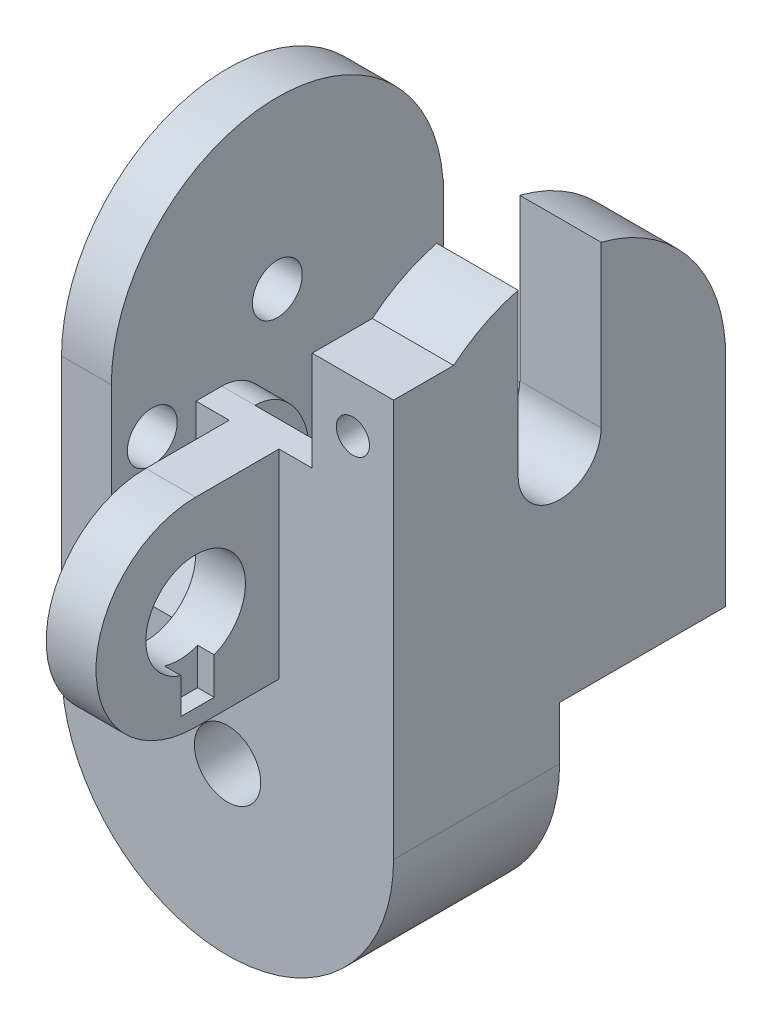
SolidWorks part; units mm, degrees
ref_plane "Front Plane" through (0, 0, 0) normal (0, 0, 1) x (1, 0, 0)
ref_plane "Top Plane" through (0, 0, 0) normal (0, 1, 0) x (1, 0, 0)
ref_plane "Right Plane" through (0, 0, 0) normal (1, 0, 0) x (0, 0, -1)
sketch "Sketch1" plane through (0, 0, 0) normal (1, 0, 0) x (0, 0, -1)
  arc A0 (9.7654, 20.1165) -> (-9.7654, 20.1165) centre (0, 22.2701) ccw
  arc A1 (-7.8874, -56.3924) -> (7.8874, -56.3924) centre (0, -57.7299) ccw
  arc A2 (-7.8874, -56.3924) -> (-9.7654, 20.1165) centre (-205.0724, -22.9549) ccw
  circle A3 centre (0, 22.2701) radius 1.5
  arc A4 (9.7654, 20.1165) -> (7.8874, -56.3924) centre (205.0724, -22.9549) ccw
  circle A5 centre (0, -57.7299) radius 2.5
extrude "Boss-Extrude1" add sketch "Sketch1" along normal blind 20
sketch "Sketch2" plane through (0, 0, 0) normal (0, 0, 1) x (1, 0, 0)
  line L1 (0, -65.7299) -> (8.1, -65.7299)
  line L2 (0, -65.7299) -> (0, -45.7299)
  line L3 (0, -45.7299) -> (8.1, -45.7299)
  line L4 (8.1, -65.7299) -> (8.1, -45.7299)
  line L5 (20, -65.7299) -> (14.8, -65.7299)
  line L6 (20, -65.7299) -> (20, -45.7299)
  line L7 (20, -45.7299) -> (14.8, -45.7299)
  line L8 (14.8, -65.7299) -> (14.8, -45.7299)
  line L11 (3, 32.2701) -> (8.1, 32.2701)
  line L12 (3, 32.2701) -> (3, 12.2701)
  line L13 (3, 12.2701) -> (8.1, 12.2701)
  line L14 (8.1, 32.2701) -> (8.1, 12.2701)
extrude "Cut-Extrude1" cut sketch "Sketch2" against normal blind 20 and the other way blind 20
sketch "Sketch3" plane through (8.1, 0, 0) normal (-1, 0, 0) x (0, 0, 1)
  line L0 (8.5, 22.2701) -> (8.5, 40.9095)
  line L1 (8.5, 40.9095) -> (-17.5287, 40.9095)
  line L2 (-17.5287, 40.9095) -> (-17.5287, 13.7701)
  line L3 (0, 13.7701) -> (-17.5287, 13.7701)
  arc A0 (0, 13.7701) -> (8.5, 22.2701) centre (0, 22.2701) ccw
extrude "Cut-Extrude2" cut sketch "Sketch3" against normal blind 9
sketch "Sketch4" plane through (8.1, 0, 0) normal (-1, 0, 0) x (0, 0, 1)
  line L0 (8.5, 27.5379) -> (8.2838, 12.7416)
  line L1 (8.2838, 12.7416) -> (10.2838, 12.7416)
  line L2 (10.2838, 12.7416) -> (10.2838, 27.5379)
  line L3 (10.2838, 27.5379) -> (8.5, 27.5379)
  arc A0 (9.7654, 20.1165) -> (6.3734, -45.7299) centre (205.0724, -22.9549) ccw construction
extrude "Boss-Extrude2" add sketch "Sketch4" against normal through all
sketch "Sketch5" plane through (8.1, 0, 0) normal (-1, 0, 0) x (0, 0, 1)
  line L4 (8.1452, 11.9686) -> (8.4478, 23.9686)
  line L6 (15.0224, 23.9686) -> (9.8547, 23.9686)
  line L8 (8.1452, 11.9686) -> (15.0224, 11.9686)
  line L9 (8.5, 27.5379) -> (8.4045, 20.9993) construction
  line L10 (8.4478, 23.9686) -> (9.8547, 23.9686)
  circle A2 centre (15.0224, 17.9686) radius 3
  arc A5 (15.0224, 11.9686) -> (15.0224, 23.9686) centre (15.0224, 17.9686) ccw
  arc A6 (9.7654, 20.1165) -> (-9.7654, 20.1165) centre (0, 22.2701) ccw construction
  arc A7 (9.7654, 20.1165) -> (6.3734, -45.7299) centre (205.0724, -22.9549) ccw construction
extrude "Boss-Extrude3" add sketch "Sketch5" against normal blind 5
sketch "Sketch12" plane through (13.1, 0, 0) normal (1, 0, 0) x (0, 0, -1)
  line L2 (-13.9029, 14.9686) -> (-13.9029, 12.9686)
  line L4 (-15.9029, 14.9686) -> (-15.9029, 15.2943)
  line L5 (-15.9029, 15.2943) -> (-13.9029, 15.2943)
  line L6 (-13.9029, 12.9686) -> (-15.9029, 12.9686)
  line L7 (-13.9029, 14.9686) -> (-13.9029, 15.2943)
  line L11 (-15.9029, 14.9686) -> (-15.9029, 12.9686)
extrude "Cut-Extrude6" cut sketch "Sketch12" against normal blind 1
sketch "Sketch13" plane through (17.1, 0, 0) normal (-1, 0, 0) x (0, 0, 1)
  circle A0 centre (0, 22.2701) radius 2.5
extrude "Cut-Extrude7" cut sketch "Sketch13" against normal blind 4
sketch "Sketch15" plane through (0, 0, 0) normal (-1, 0, 0) x (0, 0, 1)
  line L0 (10, 22.2701) -> (10, 11.9686)
  line L1 (8.1452, 11.9686) -> (15.0224, 11.9686) construction
  line L2 (10, 11.9686) -> (8.1452, 11.9686)
  line L3 (10, 22.2701) -> (7.5957, 11.9686)
  line L4 (7.5957, 11.9686) -> (8.1452, 11.9686)
  arc A0 (9.7654, 20.1165) -> (-9.7654, 20.1165) centre (0, 22.2701) ccw construction
extrude "Boss-Extrude4" add sketch "Sketch15" against normal blind 3
sketch "Sketch16" plane through (20, 0, 0) normal (1, 0, 0) x (0, 0, -1)
  line L0 (-10.2838, 23.9686) -> (-9.8547, 23.9686)
  line L1 (-10.2838, 23.9686) -> (-10.2838, 27.5379)
  line L2 (-10.2838, 27.5379) -> (-8.5, 27.5379) construction
  line L3 (-10.2838, 12.7416) -> (-10.2838, 27.5379) construction
  line L4 (-10.2838, 27.5379) -> (-8.5, 27.5379)
  arc A0 (-8.5, 27.5379) -> (-9.8547, 23.9686) centre (0, 22.2701) ccw
extrude "Cut-Extrude9" cut sketch "Sketch16" against normal blind 3
sketch "Sketch17" plane through (0, 0, 10.2838) normal (0, 0, 1) x (1, 0, 0)
  line L1 (17.1, 27.5379) -> (8.1, 27.5379)
  line L2 (17.1, 27.5379) -> (17.1, 23.9686)
  line L3 (17.1, 23.9686) -> (8.1, 23.9686)
  line L4 (8.1, 27.5379) -> (8.1, 23.9686)
extrude "Cut-Extrude11" cut sketch "Sketch17" against normal blind 3
sketch "Sketch18" plane through (13.1, 0, 0) normal (1, 0, 0) x (0, 0, -1)
  line L1 (-10.2838, 12.7416) -> (-4.5128, 12.7416)
  line L2 (-10.2838, 12.7416) -> (-10.2838, 11.9686)
  line L3 (-10.2838, 11.9686) -> (-4.5128, 11.9686)
  line L4 (-4.5128, 12.7416) -> (-4.5128, 11.9686)
extrude "Boss-Extrude5" add sketch "Sketch18" along normal through all and the other way blind 1
sketch "Sketch19" plane through (0, 12.2701, 0) normal (0, 1, 0) x (1, 0, 0)
  line L1 (8.1, -8.1989) -> (3, -8.1989)
  line L2 (8.1, -8.1989) -> (8.1, 8.1989)
  line L3 (8.1, 8.1989) -> (3, 8.1989)
  line L4 (3, -8.1989) -> (3, 8.1989)
extrude "Cut-Extrude12" cut sketch "Sketch19" against normal up to surface (0.3015 mm away) up to face at (1.5, 11.9686, 9.0726)
sketch "Sketch20" plane through (17.1, 0, 0) normal (-1, 0, 0) x (0, 0, 1)
  line L1 (2.5, 22.2701) -> (-2.5, 22.2701)
  line L2 (2.5, 22.2701) -> (2.5, 34.6894)
  line L3 (2.5, 34.6894) -> (-2.5, 34.6894)
  line L4 (-2.5, 22.2701) -> (-2.5, 34.6894)
  circle A0 centre (0, 22.2701) radius 2.5 construction
extrude "Cut-Extrude13" cut sketch "Sketch20" against normal blind 10
sketch "Sketch21" plane through (17.1, 0, 0) normal (-1, 0, 0) x (0, 0, 1)
  line L1 (-8.4732, 13.7701) -> (0.2785, 12.274)
  line L3 (2.5, 22.2701) -> (2.5, 31.9526)
  line L5 (-2.5, 22.2701) -> (-2.5, 31.9526)
  arc A0 (0.2785, 12.274) -> (2.5, 31.9526) centre (0, 22.2701) ccw
  arc A1 (-2.5, 22.2701) -> (2.5, 22.2701) centre (0, 22.2701) ccw
  arc A2 (-2.5, 31.9526) -> (-9.7654, 20.1165) centre (0, 22.2701) ccw
  arc A7 (-8.4732, 13.7701) -> (-9.7654, 20.1165) centre (-205.0724, -22.9549) ccw
extrude "Boss-Extrude6" add sketch "Sketch21" along normal blind 2
sketch "Sketch23" plane through (0, 0, 10.2838) normal (0, 0, 1) x (1, 0, 0)
  line L1 (15.1, 23.9686) -> (20, 23.9686)
  line L2 (15.1, 23.9686) -> (15.1, 29.9686)
  line L3 (15.1, 29.9686) -> (20, 29.9686)
  line L4 (20, 23.9686) -> (20, 29.9686)
extrude "Boss-Extrude7" add sketch "Sketch23" against normal blind 4
sketch "Sketch22" plane through (0, 0, 10.2838) normal (0, 0, 1) x (1, 0, 0)
  circle A1 centre (17.55, 26.8701) radius 1
extrude "Cut-Extrude15" cut sketch "Sketch22" against normal blind 8
sketch "Sketch24" plane through (8.1, 0, 0) normal (-1, 0, 0) x (0, 0, 1)
  line L0 (5.1478, 19.7374) -> (5.1478, 15.5063)
  line L2 (8.4478, 23.9686) -> (8.4478, 15.5063)
  line L3 (8.4478, 15.5063) -> (5.1478, 15.5063)
  arc A0 (0, 13.7701) -> (8.3673, 20.7738) centre (0, 22.2701) ccw construction
  ellipse E0 centre (8.4478, 19.7374) end of major axis (8.4478, 15.5063) minor radius 3.3 (8.4478, 23.9686) -> (5.1478, 19.7374) ccw
extrude "Boss-Extrude8" add sketch "Sketch24" against normal blind 2
sketch "Sketch14" plane through (0, 0, 0) normal (-1, 0, 0) x (0, 0, 1)
  circle A3 centre (7.5326, 18.3318) radius 1.5
extrude "Cut-Extrude8" cut sketch "Sketch14" against normal up to surface (10.1 mm away) up to face at (10.1, 20.14, 6.7306)
sketch "Sketch25" plane through (8.1, 0, 0) normal (-1, 0, 0) x (0, 0, 1)
  line L0 (12, -45.7299) -> (8.3462, -36.9607)
  line L1 (-12, -45.7299) -> (-12, -57.7299)
  line L2 (12, -45.7299) -> (12, -57.7299)
  line L3 (-12, -45.7299) -> (-8.3462, -36.9607)
  line L5 (2.5, -53.2274) -> (2.5, -45.7299)
  line L7 (-2.5, -53.2274) -> (-2.5, -45.7299)
  arc A0 (-2.5, -53.2274) -> (2.5, -53.2274) centre (0, -57.7299) ccw
  arc A1 (-12, -57.7299) -> (12, -57.7299) centre (0, -57.7299) ccw
  arc A2 (2.5, -45.7299) -> (8.3462, -36.9607) centre (0, -37.7299) ccw
  arc A4 (-8.3462, -36.9607) -> (-2.5, -45.7299) centre (0, -37.7299) ccw
extrude "Cut-Extrude17" cut sketch "Sketch25" against normal blind 2 and the other way up to surface (8.1 mm away) other way up to face at (0, 18.3318, 9.0326)
sketch "Sketch26" plane through (20, 0, 0) normal (1, 0, 0) x (0, 0, -1)
  line L0 (-10.2838, 11.9686) -> (-10.2838, 29.9686) construction
  line L1 (-7.21, 15.0854) -> (-10.2838, 15.0854)
  line L3 (-7.21, 17.0854) -> (-10.2838, 17.0854)
  line L4 (-10.2838, 15.0854) -> (-10.2838, 17.0854)
  line L8 (-1.6082, -37.73) -> (0.397, -37.73)
  arc A0 (-4.2066, 12.6671) -> (-7.21, 15.0854) centre (-7.21, 12.0113) ccw
  arc A1 (-2.2434, 13.0504) -> (-7.21, 17.0854) centre (-7.21, 12.0113) ccw
  arc A2 (-2.3994, -46.1854) -> (-4.2066, 12.6671) centre (-205.0724, -22.9549) ccw
  arc A3 (-1.6082, -37.73) -> (-4.2066, 12.6671) centre (-205.0724, -22.9549) ccw
  circle A4 centre (-7.21, 12.0113) radius 5.0741 construction
  circle A5 centre (-7.21, 12.0113) radius 3.0741 construction
  arc A6 (-0.4124, -46.4131) -> (-2.2373, 13.0163) centre (-205.0724, -22.9549) ccw
  arc A7 (0.397, -37.73) -> (-2.2434, 13.0504) centre (-205.0724, -22.9549) ccw
  dimension "D3" = 2
  dimension "D1" = 4
  dimension "D2" = 6
extrude "Cut-Extrude18" cut sketch "Sketch26" against normal blind 2
sketch "Sketch29" plane through (20, 0, 0) normal (1, 0, 0) x (0, 0, -1)
  line L1 (8, -37.7299) -> (8.1403, -37.7299)
  line L2 (-15.7549, -37.7299) -> (-8, -37.7299)
  line L3 (-15.7549, -37.7299) -> (-15.7549, -45.9375)
  line L4 (-15.7549, -45.9375) -> (8.1403, -45.9375)
  line L5 (8.1403, -37.7299) -> (8.1403, -45.9375)
  arc A0 (-8, -37.7299) -> (8, -37.7299) centre (0, -37.7299) ccw
extrude "Cut-Extrude20" cut sketch "Sketch29" against normal up to surface (5.2 mm away) up to face at (14.8, -57.7299, -2.5)
sketch "Sketch30" plane through (0, 0, 10.2838) normal (0, 0, 1) x (1, 0, 0)
  line L1 (13.1, 11.9686) -> (20, 11.9686)
  line L2 (13.1, 11.9686) -> (13.1, 31.9686)
  line L3 (13.1, 31.9686) -> (20, 31.9686)
  line L4 (20, 11.9686) -> (20, 31.9686)
extrude "Cut-Extrude21" cut sketch "Sketch30" against normal up to surface (0.2838 mm away) up to face at (1.5, 17.1194, 10)
sketch "Sketch31" plane through (0, 23.9686, 0) normal (0, 1, 0) x (1, 0, 0)
  line L0 (8.1, -15.0224) -> (8.1, -8.4478) construction
  line L1 (8.1, -10) -> (10.1, -10)
  line L2 (8.1, -10) -> (8.1, -21.0224)
  line L3 (8.1, -21.0224) -> (10.1, -21.0224)
  line L4 (10.1, -10) -> (10.1, -21.0224)
  line L5 (8.1, -21.0224) -> (13.1, -21.0224) construction
extrude "Cut-Extrude22" cut sketch "Sketch31" against normal up to next
sketch "Sketch32" plane through (8.1, 0, 0) normal (-1, 0, 0) x (0, 0, 1)
  line L0 (-8.4732, 13.7701) -> (-8.4732, 5.4011)
  line L2 (5.1478, 15.5063) -> (-8.4732, 5.4011)
  line L5 (5.1478, 15.5063) -> (-8.4732, 13.7701)
extrude "Cut-Extrude23" cut sketch "Sketch32" against normal blind 7
sketch "Sketch33" plane through (0, 0, 10) normal (0, 0, 1) x (1, 0, 0)
  line L1 (20, 11.9686) -> (0, 11.9686)
  line L2 (20, 11.9686) -> (20, -67.5782)
  line L3 (20, -67.5782) -> (0, -67.5782)
  line L4 (0, 11.9686) -> (0, -67.5782)
extrude "Cut-Extrude26" cut sketch "Sketch33" against normal through all contours L3 region at (10, -27.8048, 10)
sketch "Sketch36" plane through (0, 0, 10) normal (0, 0, 1) x (1, 0, 0)
  line L1 (20, 11.9686) -> (0, 11.9686)
  line L2 (20, 11.9686) -> (20, 6)
  line L4 (0, 11.9686) -> (0, 6)
  circle A0 centre (10, 6) radius 4
  arc A3 (0, 6) -> (20, 6) centre (10, 6) ccw
extrude "Boss-Extrude9" add sketch "Sketch36" against normal through all
sketch "Sketch37" plane through (0, 0, -10) normal (0, 0, -1) x (-1, 0, 0)
  line L1 (0, 11.9686) -> (-3, 11.9686)
  line L2 (0, 11.9686) -> (0, 22.9686)
  line L3 (0, 22.9686) -> (-3, 22.9686)
  line L4 (-3, 11.9686) -> (-3, 22.9686)
  line L5 (-20, 11.9686) -> (-15.1, 11.9686)
  line L6 (-20, 11.9686) -> (-20, 22.9686)
  line L7 (-20, 22.9686) -> (-15.1, 22.9686)
  line L8 (-15.1, 11.9686) -> (-15.1, 22.9686)
extrude "Boss-Extrude10" add sketch "Sketch37" against normal blind 2
sketch "Sketch39" plane through (0, 0, -10) normal (0, 0, -1) x (-1, 0, 0)
  line L0 (-8.1, 11.9686) -> (-15.1, 11.9686) construction
  line L3 (-10, 11.9686) -> (-9, 11.9686)
  line L4 (-9, 10) -> (-9, 11.9686)
  line L5 (-15.1, 11.9686) -> (-3, 11.9686) construction
  line L8 (-10, 11.9686) -> (-11, 11.9686)
  line L9 (-11, 10) -> (-11, 11.9686)
  line L12 (-11, 10) -> (-11, 9.5215)
  line L13 (-11, 9.5215) -> (-9, 9.5215)
  line L14 (-9, 10) -> (-9, 9.5215)
extrude "Cut-Extrude27" cut sketch "Sketch39" against normal blind 3
sketch "Sketch40" plane through (0, 0, 10) normal (0, 0, 1) x (1, 0, 0)
  line L0 (20, 6) -> (20, 15.0854) construction
  line L1 (18, 17.0854) -> (20, 17.0854)
  line L2 (18, 17.0854) -> (18, 8.4002)
  line L3 (18, 8.4002) -> (20, 8.4002)
  line L4 (20, 17.0854) -> (20, 8.4002)
extrude "Boss-Extrude11" add sketch "Sketch40" against normal blind 9
sketch "Sketch41" plane through (0, 0, 10) normal (0, 0, 1) x (1, 0, 0)
  circle A0 centre (10, 6) radius 4
  circle A1 centre (10, 6) radius 2
extrude "Boss-Extrude12" add sketch "Sketch41" against normal blind 5
sketch "Sketch42" plane through (0, 0, -10) normal (0, 0, -1) x (-1, 0, 0)
  line L0 (-13.543, 6) -> (-6.1735, 6)
  line L1 (0, 6) -> (0, 9.5772)
  line L5 (0, 6) -> (0, -8)
  line L7 (-20, 6) -> (-20, -8)
  line L8 (-20, 9.1962) -> (-20, 6)
  arc A1 (0, 9.5772) -> (-6.1735, 6) centre (1.5969, -0.2945) ccw
  arc A3 (-20, -8) -> (0, -8) centre (-10, -8) ccw
  arc A5 (-13.543, 6) -> (-20, 9.1962) centre (-20.9099, -0.7623) ccw
extrude "Cut-Extrude29" cut sketch "Sketch42" against normal blind 10
